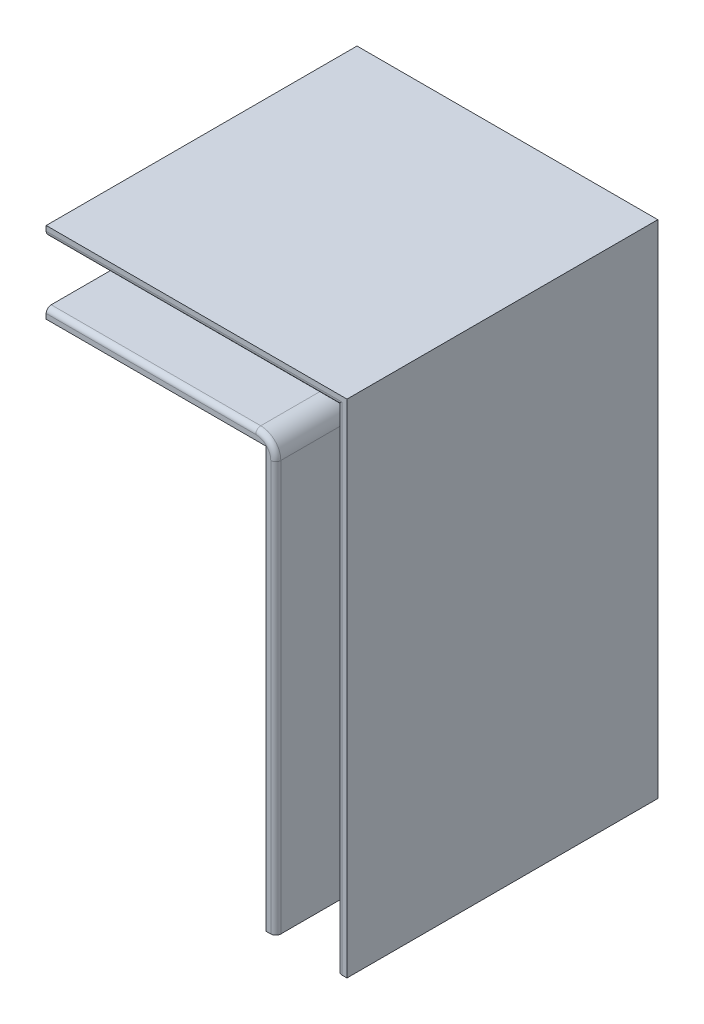
SolidWorks part; units mm, degrees
ref_plane "Front" through (0, 0, 0) normal (0, 0, 1) x (1, 0, 0)
ref_plane "Top" through (0, 0, 0) normal (0, 1, 0) x (1, 0, 0)
ref_plane "Right" through (0, 0, 0) normal (1, 0, 0) x (0, 0, -1)
sketch "Sketch1" plane through (0, 0, 0) normal (0, 0, 1) x (1, 0, 0)
  line L5 (0, 0) -> (30, 0)
  line L6 (0, 0) -> (0, 50)
  line L7 (0, 50) -> (30, 50)
  line L8 (30, 0) -> (30, 50)
  dimension "D1" = 50
  dimension "D2" = 30
extrude "Boss-Extrude1" add sketch "Sketch1" along normal blind 1
sketch "Sketch2" plane through (0, 0, 1) normal (0, 0, 1) x (1, 0, 0)
  line L0 (0, 50) -> (0, 0) construction
  line L5 (30, 0) -> (30, 50) construction
  line L15 (0, 50) -> (30, 50)
  line L16 (0, 50) -> (0, 49)
  line L17 (0, 49) -> (29, 49)
  line L18 (30, 50) -> (30, 49)
  line L19 (0, 0) -> (30, 0) construction
  line L24 (30, 49) -> (30, 0)
  line L33 (30, 0) -> (29, 0)
  line L34 (29, 49) -> (29, 0)
  line L35 (0, 42.9) -> (22.9, 42.9)
  line L36 (0, 42.9) -> (0, 41.9)
  line L37 (0, 41.9) -> (21.9, 41.9)
  line L38 (22.9, 42.9) -> (22.9, 41.9)
  line L41 (22.9, 41.9) -> (22.9, 0)
  line L42 (22.9, 0) -> (21.9, 0)
  line L43 (21.9, 41.9) -> (21.9, 0)
  dimension "D1" = 1
  dimension "D2" = 6.1
  dimension "D3" = 6.1
extrude "Boss-Extrude2" add sketch "Sketch2" along normal blind 30
fillet "Fillet1" radius 2 7 edges at (22.9, 42.9, 16) (29, 24.5, 1) (22.9, 21.45, 1) (14.5, 49, 1) (11.45, 42.9, 1) (10.95, 41.9, 1) (21.9, 20.95, 1)
fillet "Fillet2" radius 0.5 5 edges at (10.45, 42.9, 31) (22.3142, 42.3142, 31) (14.5, 49, 31) (22.9, 20.45, 31) (29, 24.5, 31)
